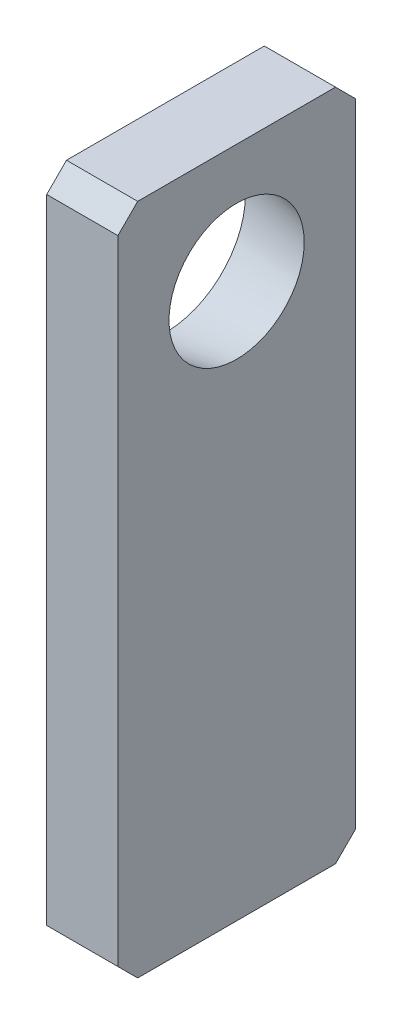
SolidWorks part; units mm, degrees
ref_plane "Front Plane" through (0, 0, 0) normal (0, 0, 1) x (1, 0, 0)
ref_plane "Top Plane" through (0, 0, 0) normal (0, 1, 0) x (1, 0, 0)
ref_plane "Right Plane" through (0, 0, 0) normal (1, 0, 0) x (0, 0, -1)
sketch "Sketch1" plane through (0, 0, 0) normal (1, 0, 0) x (0, 0, -1)
  line L5 (-7.5, 37.5) -> (7.5, 37.5)
  line L6 (-7.5, 37.5) -> (-7.5, 0)
  line L7 (-7.5, 0) -> (7.5, 0)
  line L8 (7.5, 37.5) -> (7.5, 0)
  line L9 (-7.5, 37.5) -> (7.5, 0) construction
  line L10 (-7.5, 0) -> (7.5, 37.5) construction
  circle A1 centre (0, 30) radius 5 construction
  point P0 (0, 18.75)
  point P6 (0, 30)
  dimension "D2" = 10
  dimension "D1" = 30
  dimension "D3" = 15
  dimension "D4" = 7.5
extrude "Boss-Extrude1" add sketch "Sketch1" against normal blind 4.5
ref_plane "PItch Starting Plane" through (-5, 0, 0) normal (1, 0, 0) x (0, 0, -1)
sketch "Sketch2" plane through (-5, 0, 0) normal (1, 0, 0) x (0, 0, -1)
  circle A0 centre (0, 30) radius 5 construction
  circle A1 centre (0, 30) radius 5
  point P0 (0, 30)
extrude "Cut-Extrude1" cut sketch "Sketch2" along normal blind 5 draft 10 and the other way through all contours A1 region at (-5, 30, 0)
other "Offset to account for Base Thickness" face at (-2.25, 0, 0) offset 5 parameters "D1"=5
chamfer "Chamfer1" distance 1.25 angle 45 4 edges at (-2.25, 37.5, 7.5) (-2.25, 37.5, -7.5) (-2.25, -5, 7.5) (-2.25, -5, -7.5)
other "Offset for 3D print" flip direction yes face at (-4.5, 30, -4.9118) offset 0.15 parameters "D1"=0.15
equation "\"D1@Chamfer1\"=2.5/2"
